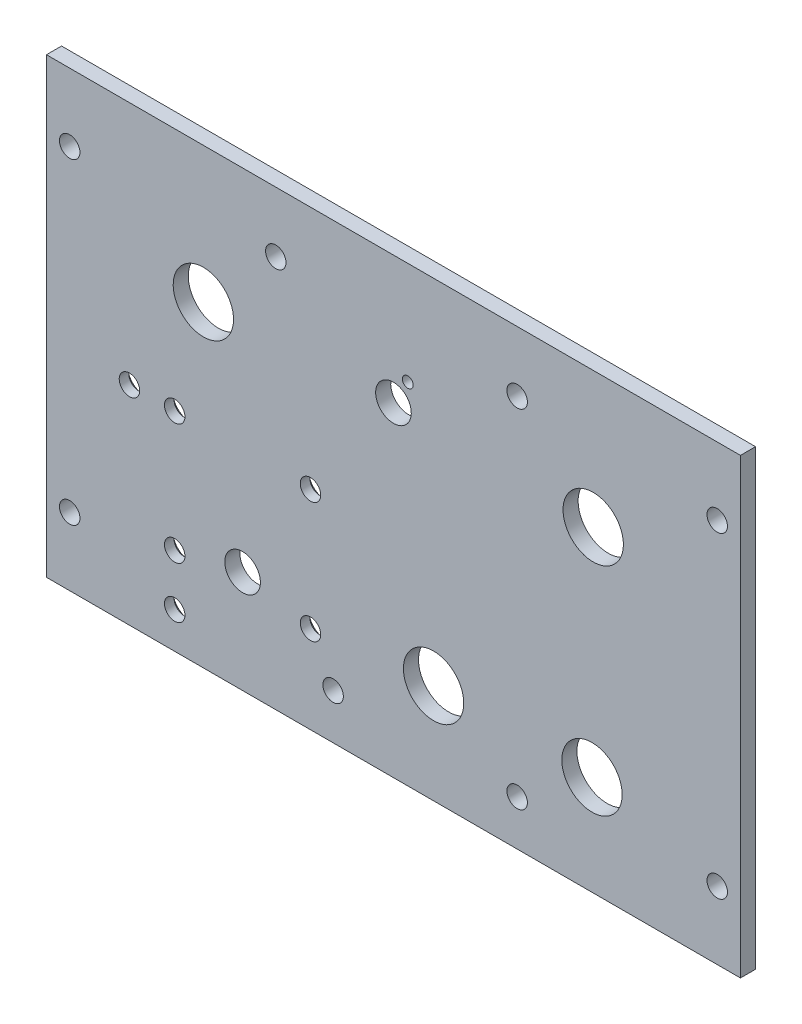
SolidWorks part; units mm, degrees
material "Acrylic (Medium-high impact)"
ref_plane "Front Plane" through (0, 0, 0) normal (0, 0, 1) x (1, 0, 0)
ref_plane "Top Plane" through (0, 0, 0) normal (0, 1, 0) x (1, 0, 0)
ref_plane "Right Plane" through (0, 0, 0) normal (1, 0, 0) x (0, 0, -1)
sketch "Sketch1" plane through (0, 0, 0) normal (0, 0, 1) x (1, 0, 0)
  line L8 (0, 95.25) -> (-146.05, 95.25)
  line L9 (-146.05, 95.25) -> (-146.05, 0)
  line L10 (-146.05, 0) -> (0, 0)
  line L11 (0, 0) -> (0, 95.25)
extrude "Boss-Extrude1" add sketch "Sketch1" against normal blind 3.175
hole_wizard "#6 Clearance Hole1" positions "Sketch3" profile "Sketch2" hole size "#6" standard "ANSI Inch" end condition through all
sketch "Sketch3" plane through (0, 0, -3.175) normal (0, 0, -1) x (-1, 0, 0)
  point P0 (4.8895, 80.9625)
  point P3 (141.1605, 80.9625)
  point P6 (141.1605, 14.2875)
  point P9 (4.8895, 14.2875)
  point P12 (46.99, 9.525)
  point P15 (85.725, 9.525)
  point P18 (97.79, 82.55)
  point P21 (46.99, 82.55)
sketch "Sketch2" plane through (-4.8895, 80.9625, -3.175) normal (1, 0, 0) x (0, 1, 0)
  line L0 (0, 0) -> (0, 3.175)
  line L1 (0, 3.175) -> (2.1526, 3.175)
  line L2 (2.1526, 3.175) -> (2.1526, 0)
  line L5 (2.1526, 0) -> (0, 0)
  line L11 (0, -6.35) -> (0, 107.95) construction
  dimension "Thru Hole Dia." = 4.3053
  dimension "Thru Hole Depth" = 3.175
sketch "Sketch5" plane through (0, 0, -7.4676) normal (0, 0, -1) x (-1, 0, 0)
  circle A0 centre (30.988, 66.675) radius 6.35
  circle A1 centre (113.03, 66.675) radius 6.35
  circle A2 centre (64.5795, 20.955) radius 6.35
  circle A3 centre (31.242, 20.955) radius 6.35
  circle A4 centre (73.025, 68.326) radius 3.75
  circle A5 centre (104.775, 21.59) radius 3.75
  dimension "D1" = 12.7
  dimension "D2" = 7.5
extrude "Cut-Extrude1" cut sketch "Sketch5" against normal through all
hole_wizard "CSK for #6 Flat Head Machine Screw (100)1" positions "Sketch7" profile "Sketch6" countersink size "#6" standard "ANSI Inch" end condition through all
sketch "Sketch7" plane through (0, 0, -3.175) normal (0, 0, -1) x (-1, 0, 0)
  point P0 (90.4875, 43.815)
  point P3 (90.4875, 18.415)
  point P6 (119.0625, 7.6362)
  point P9 (119.0625, 18.415)
  point P12 (119.0625, 43.815)
  point P15 (128.5875, 43.815)
sketch "Sketch6" plane through (-90.4875, 43.815, -3.175) normal (1, 0, 0) x (0, 1, 0)
  line L0 (0, 0) -> (0, 3.175)
  line L1 (0, 3.175) -> (2.1526, 3.175)
  line L2 (2.1526, 3.175) -> (2.1526, 1.1669)
  line L3 (2.1526, 1.1669) -> (3.5433, 0)
  line L5 (3.5433, 0) -> (0, 0)
  line L6 (-2.1526, 1.1669) -> (-3.5433, 0) construction
  line L11 (0, -6.35) -> (0, 107.95) construction
  dimension "Thru Hole Dia." = 4.3053
  dimension "Thru Hole Depth" = 3.175
  dimension "Near C'Sink Dia." = 7.0866
  dimension "Near C'Sink Angle" = 100
sketch "Sketch8" plane through (0, 0, 0) normal (0, 0, 1) x (1, 0, 0)
  circle A0 centre (-70.0124, 73.6066) radius 1.1345
extrude "Cut-Extrude2" cut sketch "Sketch8" against normal through all
